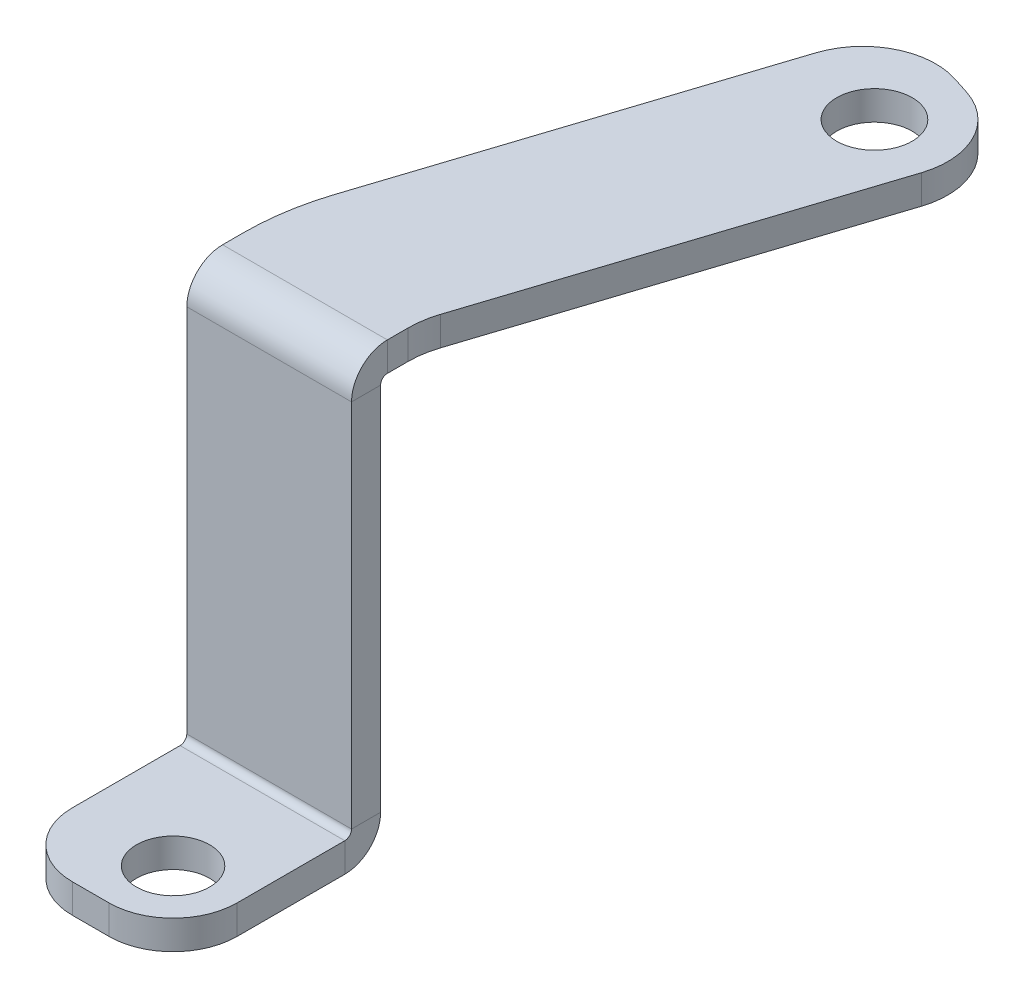
SolidWorks part; units mm, degrees
note: The reader was unsure of these and kept them because the rebuilt part matched: flange length of "Edge-Flange1", "Edge-Flange2"; thickness of "Edge-Flange1", "Edge-Flange2".
material "Copper"
ref_plane "Front Plane" through (0, 0, 0) normal (0, 0, 1) x (1, 0, 0)
ref_plane "Top Plane" through (0, 0, 0) normal (0, 1, 0) x (1, 0, 0)
ref_plane "Right Plane" through (0, 0, 0) normal (1, 0, 0) x (0, 0, -1)
sketch "Sketch1" plane through (0, 0, 0) normal (0, 1, 0) x (1, 0, 0)
  line L1 (7, 0) -> (7, 12.5)
  line L2 (7, 12.5) -> (-11, 12.5)
  line L3 (0, -7) -> (-4, -7)
  line L4 (-11, 0) -> (-11, 12.5)
  circle A0 centre (0, 0) radius 4
  arc A1 (0, -7) -> (7, 0) centre (0, 0) ccw
  arc A2 (-4, -7) -> (-11, 0) centre (-4, 0) cw
  point P11 (-10.1815, 12.5)
  dimension "D1" = 8
  dimension "D2" = 7
  dimension "D4" = 18
  dimension "D3" = 12.5
base flange "Base-Flange1" sketch "Sketch1" thickness 3.175 reverse thickness direction no parameters "D1"=0.7366
edge flange "Edge-Flange1" sketch "Sketch8" flange angle 90 flange length 45.0625 flange position material outside bend radius 0.7366 thickness 3.175 relief rectangular parameters "D6"=10
sketch "Sketch8" plane through (0, 0, -12.5) normal (0, 0, -1) x (-1, 0, 0)
  line L0 (-7, 0) -> (11, 0) construction
  line L1 (-7, 0) -> (11, 0)
  line L2 (-7, 0) -> (-7, 41.8875)
  line L3 (-7, 41.8875) -> (11, 41.8875)
  line L4 (11, 41.8875) -> (11, 0)
  line L6 (-5.25, 41.8875) -> (-20.25, 41.8875) construction
bend "EdgeBend1" bend radius 0.7366 bend angle 90 parameters "D5"=1
edge flange "Edge-Flange2" sketch "Sketch11" flange angle 90 flange length 6.175 flange position material outside bend radius 0.7366 thickness 3.175 relief rectangular parameters "D6"=10
sketch "Sketch11" plane through (0, 41.8875, -15.675) normal (0, 1, 0) x (1, 0, 0)
  line L0 (-11, 0) -> (7, 0) construction
  line L1 (-11, 0) -> (7, 0)
  line L2 (-11, 0) -> (-11, 3)
  line L4 (7, 3) -> (7, 0)
  line L7 (-11, 3) -> (7, 3)
  dimension "D1" = 3
bend "EdgeBend2" bend radius 0.7366 bend angle 90 parameters "D5"=2
sketch "Sketch12" plane through (0, 45.0625, 0) normal (0, 1, 0) x (1, 0, 0)
  line L0 (7, 18.675) -> (-11, 18.675)
  line L1 (-9.6399, 27.274) -> (3.2382, 66.9642)
  line L2 (20.3595, 61.409) -> (7.4814, 21.7188)
  line L3 (7, 16.4116) -> (7, 18.675) construction
  line L4 (-11, 18.675) -> (-11, 16.4116) construction
  line L5 (15.219, 71.4875) -> (13.3166, 72.1047)
  arc A0 (-11, 18.675) -> (-9.6399, 27.274) centre (16.8625, 18.675) cw
  arc A2 (7.4814, 21.7188) -> (7, 18.675) centre (16.8625, 18.675) ccw
  arc A3 (20.3595, 61.409) -> (15.219, 71.4875) centre (12.75, 63.878) ccw
  circle A4 centre (10.25, 63.878) radius 42.25 construction
  circle A5 centre (12.75, 63.878) radius 4.125
  arc A6 (13.3166, 72.1047) -> (3.2382, 66.9642) centre (10.8476, 64.4952) ccw
  point P19 (-1.4015, 67.9496)
  point P24 (1.7426, 67.4841)
  point P26 (13.7424, 70.8073)
  dimension "D1" = 8.25
  dimension "D2" = 8
extrude "Boss-Extrude1" add sketch "Sketch12" against normal blind 3.175
sketch "Bend-Lines1" [suppressed] plane through (0, 0, 0) normal (0, 1, 0) x (1, 0, 0)
sketch "Bounding-Box1" [suppressed] plane through (0, 0, 0) normal (0, 1, 0) x (1, 0, 0)
sheet metal parameters "Sheet-Metal1" thickness 3.175 parameters "D1"=0.7366
flat pattern "Flat-Pattern1" [suppressed]
sketch "Bend-Lines2" plane through (0, 0, 0) normal (0, 1, 0) x (1, 0, 0)
sketch3d "Bounding-Box2" [suppressed]
  line L0 (7, 12.5, 0) -> (7, -7, 0) construction
  line L1 (-7, 12.5, 0) -> (-7, -7, 0) construction
  line L2 (7, 12.5, 0) -> (-7, 12.5, 0) construction
  line L3 (7, -7, 0) -> (-7, -7, 0) construction
sheet metal parameters "Sheet-Metal2" thickness 3.175 parameters "D1"=0.7366, "D7"=2
flat pattern "Flat-Pattern1"
sketch "Bend-Lines2" plane through (0, 0, 0) normal (0, 1, 0) x (1, 0, 0)
  line L0 (7, 13.1273) -> (-7, 13.1273) construction
  line L1 (7, 13.1273) -> (-7, 13.1273) construction
sketch3d "Bounding-Box2" [suppressed]
  line L0 (7, 56.8171, 0) -> (7, -7, 0) construction
  line L1 (-7, 56.8171, 0) -> (-7, -7, 0) construction
  line L2 (7, 56.8171, 0) -> (-7, 56.8171, 0) construction
  line L3 (7, -7, 0) -> (-7, -7, 0) construction
bend of the flat pattern "Flatten-<EdgeBend1>1"
sheet metal parameters "Sheet-Metal3" thickness 3.175 parameters "D1"=0.7366, "D7"=2
flat pattern "Flat-Pattern1"
sketch "Bend-Lines2" plane through (0, 0, 0) normal (0, 1, 0) x (1, 0, 0)
  line L0 (7, 13.1273) -> (-7, 13.1273) construction
  line L1 (7, 13.1273) -> (-7, 13.1273) construction
  line L2 (7, 57.4445) -> (-7, 57.4445) construction
  line L3 (7, 57.4445) -> (-7, 57.4445) construction
sketch3d "Bounding-Box2" [suppressed]
  line L0 (7, 61.0718, 0) -> (7, -7, 0) construction
  line L1 (-7, 61.0718, 0) -> (-7, -7, 0) construction
  line L2 (7, 61.0718, 0) -> (-7, 61.0718, 0) construction
  line L3 (7, -7, 0) -> (-7, -7, 0) construction
bend of the flat pattern "Flatten-<EdgeBend1>1"
bend of the flat pattern "Flatten-<EdgeBend2>1"
sheet metal parameters "Sheet-Metal4" thickness 3.175 parameters "D1"=0.7366, "D7"=2
flat pattern "Flat-Pattern1"
sketch "Bend-Lines2" plane through (0, 0, 0) normal (0, 1, 0) x (1, 0, 0)
  line L0 (7, 13.5887) -> (-11, 13.5887) construction
  line L1 (7, 13.5887) -> (-11, 13.5887) construction
  line L2 (7, 57.6537) -> (-11, 57.6537) construction
  line L3 (7, 57.6537) -> (-11, 57.6537) construction
sketch3d "Bounding-Box2" [suppressed]
  line L0 (21.7525, 114.2258, 0) -> (5.9845, -8.3422, 0) construction
  line L1 (-4.0507, 117.5453, 0) -> (-19.8187, -5.0227, 0) construction
  line L2 (21.7525, 114.2258, 0) -> (-4.0507, 117.5453, 0) construction
  line L3 (5.9845, -8.3422, 0) -> (-19.8187, -5.0227, 0) construction
bend of the flat pattern "Flatten-<EdgeBend1>1"
bend of the flat pattern "Flatten-<EdgeBend2>1"
